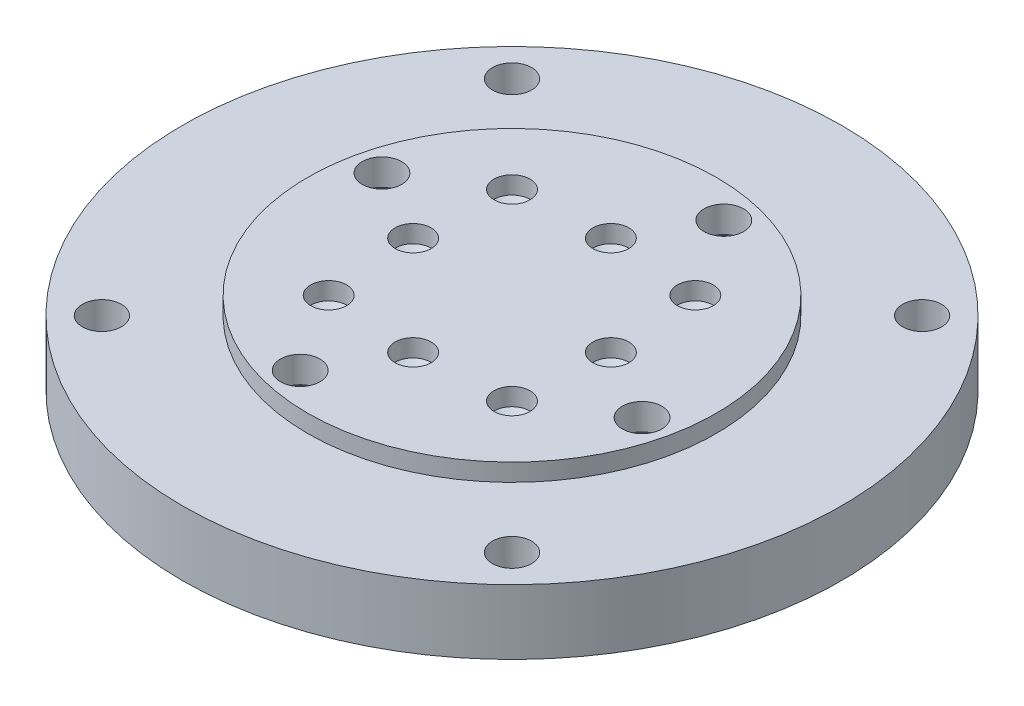
SolidWorks part; units mm, degrees
material "1060 Alloy"
ref_plane "Front Plane" through (0, 0, 0) normal (0, 0, 1) x (1, 0, 0)
ref_plane "Top Plane" through (0, 0, 0) normal (0, 1, 0) x (1, 0, 0)
ref_plane "Right Plane" through (0, 0, 0) normal (1, 0, 0) x (0, 0, -1)
ref_axis "Y Axis" through (0, 0.1588, 0) along (0, -1, 0)
sketch "outer" plane through (0, 0, 0) normal (0, 1, 0) x (1, 0, 0)
  circle A0 centre (0, 0) radius 19.05
  dimension "D1" = 38.1
extrude "Body" add sketch "outer" against normal blind 4.7625
sketch "Screw Position" plane through (0, 0, 0) normal (0, 1, 0) x (1, 0, 0)
  point P0 (-11.8539, 11.8539)
  dimension "D1" = 16.764
hole_wizard "#4-40 Tapped Hole" positions "Sketch12" profile "Sketch13" tap size "#4-40" standard "ANSI Inch" end condition through all
sketch "Sketch12" plane through (0, 0, 0) normal (0, 1, 0) x (1, 0, 0)
  point P0 (-11.8539, 11.8539)
sketch "Sketch13" plane through (-11.8539, 0, -11.8539) normal (1, 0, 0) x (0, 0, 1)
  line L0 (0, 0) -> (0, 4.7625)
  line L1 (0, 4.7625) -> (1.1303, 4.7625)
  line L2 (1.1303, 4.7625) -> (1.1303, 0)
  line L5 (1.1303, 0) -> (0, 0)
  line L11 (0, -6.35) -> (0, 107.95) construction
  dimension "Thru Tap Drill Dia." = 2.2606
  dimension "Thru Tap Drill Depth" = 4.7625
cosmetic thread "Hole Thread3" parameters "D2"=2.8448
pattern_circular "Screw Holes" count 4 over 360 about axis through (0, 0.1588, 0) along (0, -1, 0) of "#4-40 Tapped Hole"
sketch "Inset" plane through (0, 0, 0) normal (0, 1, 0) x (1, 0, 0)
  circle A0 centre (0, 0) radius 11.811
  circle A1 centre (0, 0) radius 19.05
  dimension "D1" = 23.622
sketch "IO Hole Location" plane through (0, 0, 0) normal (0, 1, 0) x (1, 0, 0)
  line L0 (-19.05, 0) -> (19.05, 0) construction
  circle A0 centre (0, 0) radius 10.16 construction
  circle A1 centre (0, 0) radius 19.05 construction
  point P0 (-2.3622, 9.8816)
  point P10 (-2.3622, -9.8816)
  dimension "D2" = 20.32
  dimension "D1" = 2.3622
hole_wizard "#44 (0.087) Diameter Hole1" positions "Sketch36" profile "Sketch37" hole size "#44" standard "ANSI Inch" end condition through all
sketch "Sketch36" plane through (0, 0, 0) normal (0, 1, 0) x (1, 0, 0)
  point P3 (-2.3622, -9.8816)
sketch "Sketch37" plane through (-2.3622, 0, 9.8816) normal (1, 0, 0) x (0, 0, 1)
  line L0 (0, 0) -> (0, 4.7625)
  line L1 (0, 4.7625) -> (1.1049, 4.7625)
  line L2 (1.1049, 4.7625) -> (1.1049, 0)
  line L5 (1.1049, 0) -> (0, 0)
  line L11 (0, -6.35) -> (0, 107.95) construction
  dimension "Thru Hole Dia." = 2.2098
  dimension "Thru Hole Depth" = 4.7625
hole_wizard "#43 (0.09) Diameter Hole1" positions "Sketch38" profile "Sketch40" hole size "#43" standard "ANSI Inch"
sketch "Sketch38" plane through (0, 0, 0) normal (0, 1, 0) x (1, 0, 0)
  point P3 (-2.3622, -9.8816)
sketch "Sketch40" plane through (-2.3622, 0, 9.8816) normal (1, 0, 0) x (0, 0, 1)
  line L0 (0, 0) -> (0, 2.2108)
  line L1 (0, 2.2108) -> (1.143, 1.524)
  line L2 (1.143, 1.524) -> (1.143, 0)
  line L5 (1.143, 0) -> (0, 0)
  line L10 (0, 2.2108) -> (-1.143, 1.524) construction
  line L11 (0, -6.35) -> (0, 107.95) construction
  dimension "Hole Dia." = 2.286
  dimension "Hole Depth" = 1.524
  dimension "Drill Angle" = 118
hole_wizard "#43 (0.09) Diameter Hole2" positions "Sketch41" profile "Sketch42" hole size "#43" standard "ANSI Inch"
sketch "Sketch41" plane through (0, -4.7625, 0) normal (0, -1, 0) x (-1, 0, 0)
  point P3 (2.3622, -9.8816)
sketch "Sketch42" plane through (-2.3622, -4.7625, 9.8816) normal (1, 0, 0) x (0, 0, -1)
  line L0 (0, 0) -> (0, 2.2108)
  line L1 (0, 2.2108) -> (1.143, 1.524)
  line L2 (1.143, 1.524) -> (1.143, 0)
  line L5 (1.143, 0) -> (0, 0)
  line L10 (0, 2.2108) -> (-1.143, 1.524) construction
  line L11 (0, -6.35) -> (0, 107.95) construction
  dimension "Hole Dia." = 2.286
  dimension "Hole Depth" = 1.524
  dimension "Drill Angle" = 118
pattern_circular "IO Holes Pattern" count 4 over 360 about axis through (0, 0.1588, 0) along (0, -1, 0) of "#44 (0.087) Diameter Hole1", "#43 (0.09) Diameter Hole1", "#43 (0.09) Diameter Hole2"
sketch "Post Bottom Location" plane through (0, 0, 0) normal (0, 1, 0) x (1, 0, 0)
  point P0 (0, 5.715)
  point P1 (-5.2984, 5.2984)
  dimension "D1" = 5.715
extrude "Inset Cut" cut sketch "Inset" against normal blind 1.016
hole_wizard "#45 (0.082) Diameter Hole1" positions "Sketch44" profile "Sketch45" hole size "#45" standard "ANSI Inch"
sketch "Sketch44" plane through (0, 0, 0) normal (0, 1, 0) x (1, 0, 0)
  point P0 (0, 5.715)
  point P3 (-5.2984, 5.2984)
sketch "Sketch45" plane through (0, 0, -5.715) normal (1, 0, 0) x (0, 0, 1)
  line L0 (0, 0) -> (0, 1.6407)
  line L1 (0, 1.6407) -> (1.0414, 1.015)
  line L2 (1.0414, 1.015) -> (1.0414, 0)
  line L5 (1.0414, 0) -> (0, 0)
  line L10 (0, 1.6407) -> (-1.0414, 1.015) construction
  line L11 (0, -6.35) -> (0, 107.95) construction
  dimension "Hole Dia." = 2.0828
  dimension "Hole Depth" = 1.015
  dimension "Drill Angle" = 118
pattern_circular "Post Bottoms" count 4 over 360 about axis through (0, 0.1588, 0) along (0, -1, 0) of "#45 (0.082) Diameter Hole1"
sketch "v_sketch" plane through (0, 0, 0) normal (0, 0, 1) x (1, 0, 0)
  line L0 (19.05, -1.016) -> (-19.05, -1.016) construction
  line L1 (-13.97, -1.397) -> (-13.97, -1.016) construction
  line L2 (-13.97, -1.397) -> (-13.3359, -1.016)
  line L3 (-13.97, -1.397) -> (-14.6041, -1.016)
  line L4 (-14.6041, -1.016) -> (-13.3359, -1.016)
  point P0 (-13.97, -1.016)
  point P1 (-13.97, -1.397)
  dimension "D1" = 13.97
  dimension "D3" = 59
revolve "V cut" [suppressed] cut sketch "v_sketch" angle 360 about axis through (0, 0.1588, 0) along (0, -1, 0)
sketch "Flat Cut Sketch" plane through (0, 0, 0) normal (0, 1, 0) x (1, 0, 0)
  line L0 (0, 19.05) -> (0, -19.05) construction
  line L1 (17.78, -19.05) -> (20.32, -19.05)
  line L2 (17.78, -19.05) -> (17.78, 19.05)
  line L3 (17.78, 19.05) -> (20.32, 19.05)
  line L4 (20.32, -19.05) -> (20.32, 19.05)
  line L5 (17.78, -19.05) -> (20.32, 19.05) construction
  line L6 (17.78, 19.05) -> (20.32, -19.05) construction
  line L7 (-17.78, 19.05) -> (-20.32, -19.05) construction
  line L8 (-17.78, -19.05) -> (-20.32, 19.05) construction
  line L9 (-20.32, -19.05) -> (-20.32, 19.05)
  line L10 (-17.78, 19.05) -> (-20.32, 19.05)
  line L11 (-17.78, -19.05) -> (-17.78, 19.05)
  line L12 (-17.78, -19.05) -> (-20.32, -19.05)
  circle A0 centre (0, 0) radius 19.05 construction
  point P0 (19.05, 0)
  point P15 (-19.05, 0)
  dimension "D1" = 38.1
extrude "Flat Cut" [suppressed] cut sketch "Flat Cut Sketch" against normal through all
equation "\"outer_d\"= 3 / 2in"
equation "\"screw_r\"= 0.66in"
equation "\"inner_d\"= 0.930in"
equation "\"bottom_h\"= 3 / 16in"
equation "\"pocket_h\"= 0.060in"
equation "\"screw_inner_r\"= 0.415in"
equation "\"io_r\"= 0.4in"
equation "\"D1@outer\" = \"outer_d\""
equation "\"D1@Body\" = \"bottom_h\""
equation "\"D1@Inset\" = \"inner_d\""
equation "\"D1@Screw Position\" = \"screw_r\""
equation "\"post_r1\"= 0.225"
equation "\"post_r2\" = 0.295"
equation "\"D1@Post Bottom Location\" = \"post_r1\""
equation "\"D2@Post Bottom Location\" = \"post_r2\""
equation "\"post_bottom_h\"= 0.04in"
equation "\"D2@IO Hole Location\"=\"io_r\" * 2"
equation "\"io_x\"= 0.093in"
equation "\"D1@IO Hole Location\"=\"io_x\""
equation "\"inset_h\"= 0.04in"
equation "\"D1@Inset Cut\" = \"inset_h\""
equation "\"v_r\"= 0.55in"
equation "\"D1@v_sketch\" = \"v_r\""
equation "\"v_h\"= 0.015in"
equation "\"v_angle\"= 118"
equation "\"D3@v_sketch\" = \"v_angle\" / 2"
equation "\"D2@v_sketch\"=\"v_h\""
equation "\"flat_cut\"= 0.05in"
equation "\"D1@Flat Cut Sketch\" = \"outer_d\""
equation "\"D2@Flat Cut Sketch\" = \"flat_cut\" * 2"
